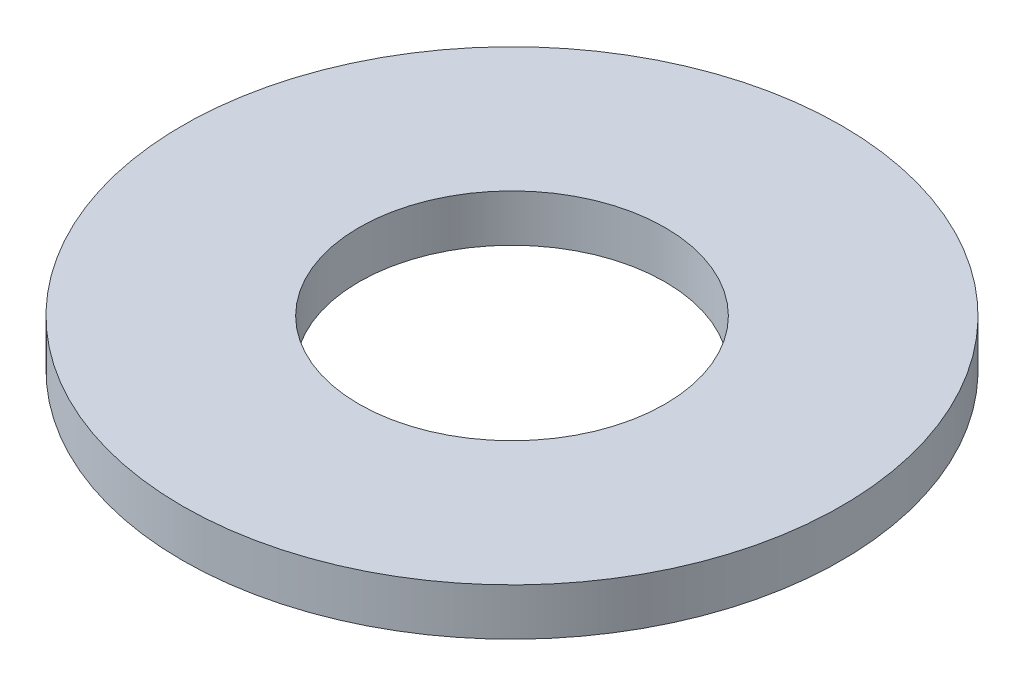
SolidWorks part; units mm, degrees
ref_plane "Front Plane" through (0, 0, 0) normal (0, 0, 1) x (1, 0, 0)
ref_plane "Top Plane" through (0, 0, 0) normal (0, 1, 0) x (1, 0, 0)
ref_plane "Right Plane" through (0, 0, 0) normal (1, 0, 0) x (0, 0, -1)
sketch "Sketch1" plane through (0, 0, 0) normal (0, 1, 0) x (1, 0, 0)
  circle A0 centre (0, 0) radius 70
  dimension "FLANGE_OD" = 140
extrude "Boss-Extrude1" add sketch "Sketch1" along normal blind 10
sketch "Sketch2" plane through (0, 0, 0) normal (0, 1, 0) x (1, 0, 0)
  circle A0 centre (0, 0) radius 32.5
  dimension "BORE_D" = 65
extrude "Cut-Extrude1" cut sketch "Sketch2" along normal through all
sketch "Sketch3" plane through (0, 10, 0) normal (0, 1, 0) x (1, 0, 0)
  circle A0 centre (0, 0) radius 29.1805 construction
  circle A1 centre (-29.1805, 0) radius 2.807
  dimension "BOLT_D" = 5.6139
  dimension "BOLT_PCD" = 58.361
extrude "Cut-Extrude2" cut sketch "Sketch3" against normal blind 8.0151 rebuild error yes
pattern_circular "CirPattern1" count 5 over 360 rebuild error yes
